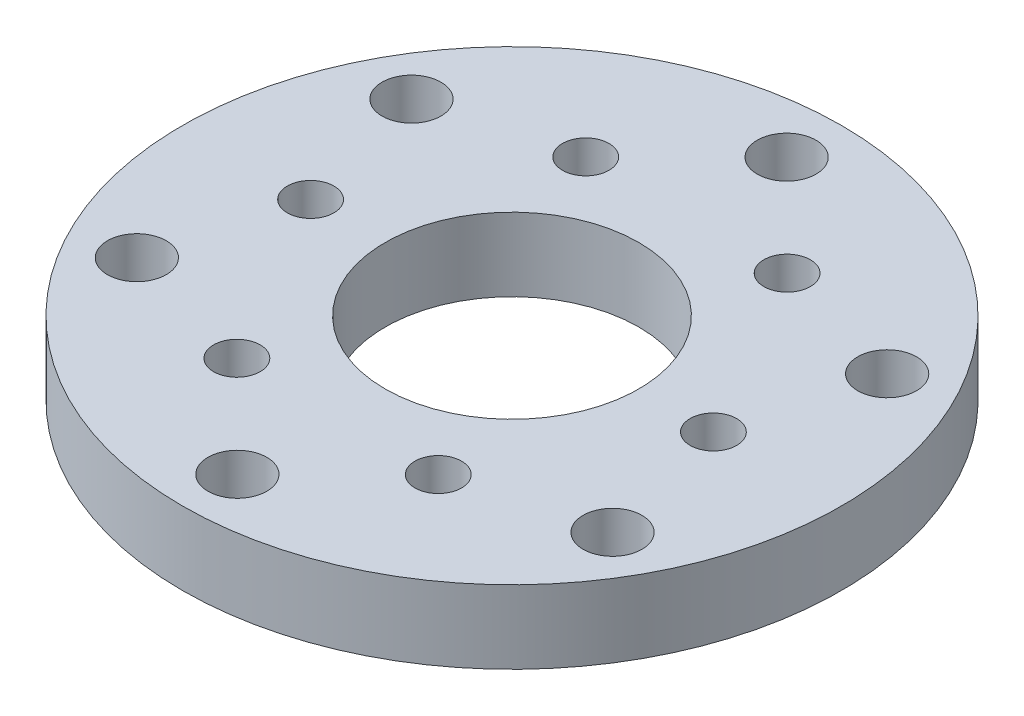
SolidWorks part; units mm, degrees
material "6061-T6 (SS)"
ref_plane "Front Plane" through (0, 0, 0) normal (0, 0, 1) x (1, 0, 0)
ref_plane "Top Plane" through (0, 0, 0) normal (0, 1, 0) x (1, 0, 0)
ref_plane "Right Plane" through (0, 0, 0) normal (1, 0, 0) x (0, 0, -1)
sketch "Sketch1" plane through (0, 0, 0) normal (0, 1, 0) x (1, 0, 0)
  circle A0 centre (0, 0) radius 28.575
  dimension "D1" = 57.15
extrude "Boss-Extrude1" add sketch "Sketch1" along normal blind 6.35
hole_wizard "1/4-20 Tapped Hole1" positions "Sketch3" profile "Sketch4" tap size "1/4-20" standard "ANSI Inch" end condition through all
sketch "Sketch3" plane through (0, 6.35, 0) normal (0, 1, 0) x (1, 0, 0)
  line L0 (0, 0) -> (0, 23.8125) construction
  circle A0 centre (0, 0) radius 23.8125
  point P0 (0, 23.8125)
  point P22 (20.6222, 11.9063)
  point P23 (20.6222, -11.9062)
  point P24 (0, -23.8125)
  point P25 (-20.6222, -11.9063)
  point P26 (-20.6222, 11.9062)
  point P28 (0, 0)
  point P29 (-23.0285, 6.0601)
  point P30 (0, 0)
  dimension "D1" = 47.625
  dimension "D2" = 6
sketch "Sketch4" plane through (0, 6.35, -23.8125) normal (1, 0, 0) x (0, 0, 1)
  line L0 (0, 0) -> (0, 6.35)
  line L1 (0, 6.35) -> (2.5527, 6.35)
  line L2 (2.5527, 6.35) -> (2.5527, 0)
  line L5 (2.5527, 0) -> (0, 0)
  line L11 (0, -6.35) -> (0, 107.95) construction
  dimension "Thru Tap Drill Dia." = 5.1054
  dimension "Thru Tap Drill Depth" = 6.35
cosmetic thread "Hole Thread1" parameters "D2"=6.35
cosmetic thread "Hole Thread2" parameters "D2"=6.35
cosmetic thread "Hole Thread3" parameters "D2"=6.35
cosmetic thread "Hole Thread4" parameters "D2"=6.35
cosmetic thread "Hole Thread5" parameters "D2"=6.35
cosmetic thread "Hole Thread6" parameters "D2"=6.35
sketch "Sketch5" plane through (0, 6.35, 0) normal (0, 1, 0) x (1, 0, 0)
  circle A0 centre (0, 0) radius 11
  dimension "D1" = 22
extrude "Cut-Extrude1" cut sketch "Sketch5" against normal through all
hole_wizard "#10-32 Tapped Hole1" positions "Sketch7" profile "Sketch8" tap size "#10-32" standard "ANSI Inch" end condition through all
sketch "Sketch7" plane through (0, 6.35, 0) normal (0, 1, 0) x (1, 0, 0)
  line L0 (0, 0) -> (-8.7313, 15.123) construction
  line L2 (0, 0) -> (0, 17.4625) construction
  circle A0 centre (0, 0) radius 17.4625
  point P0 (-8.7313, 15.123)
  point P22 (8.7312, 15.123)
  point P23 (17.4625, 0)
  point P24 (8.7313, -15.123)
  point P25 (-8.7312, -15.123)
  point P26 (-17.4625, 0)
  point P28 (0, 0)
  point P29 (0, 0)
  dimension "D1" = 34.925
  dimension "D2" = 30
  dimension "D3" = 6
sketch "Sketch8" plane through (-8.7313, 6.35, -15.123) normal (1, 0, 0) x (0, 0, 1)
  line L0 (0, 0) -> (0, 6.35)
  line L1 (0, 6.35) -> (2.0193, 6.35)
  line L2 (2.0193, 6.35) -> (2.0193, 0)
  line L5 (2.0193, 0) -> (0, 0)
  line L11 (0, -6.35) -> (0, 107.95) construction
  dimension "Thru Tap Drill Dia." = 4.0386
  dimension "Thru Tap Drill Depth" = 6.35
cosmetic thread "Hole Thread7" parameters "D2"=4.826
cosmetic thread "Hole Thread8" parameters "D2"=4.826
cosmetic thread "Hole Thread9" parameters "D2"=4.826
cosmetic thread "Hole Thread10" parameters "D2"=4.826
cosmetic thread "Hole Thread11" parameters "D2"=4.826
cosmetic thread "Hole Thread12" parameters "D2"=4.826
